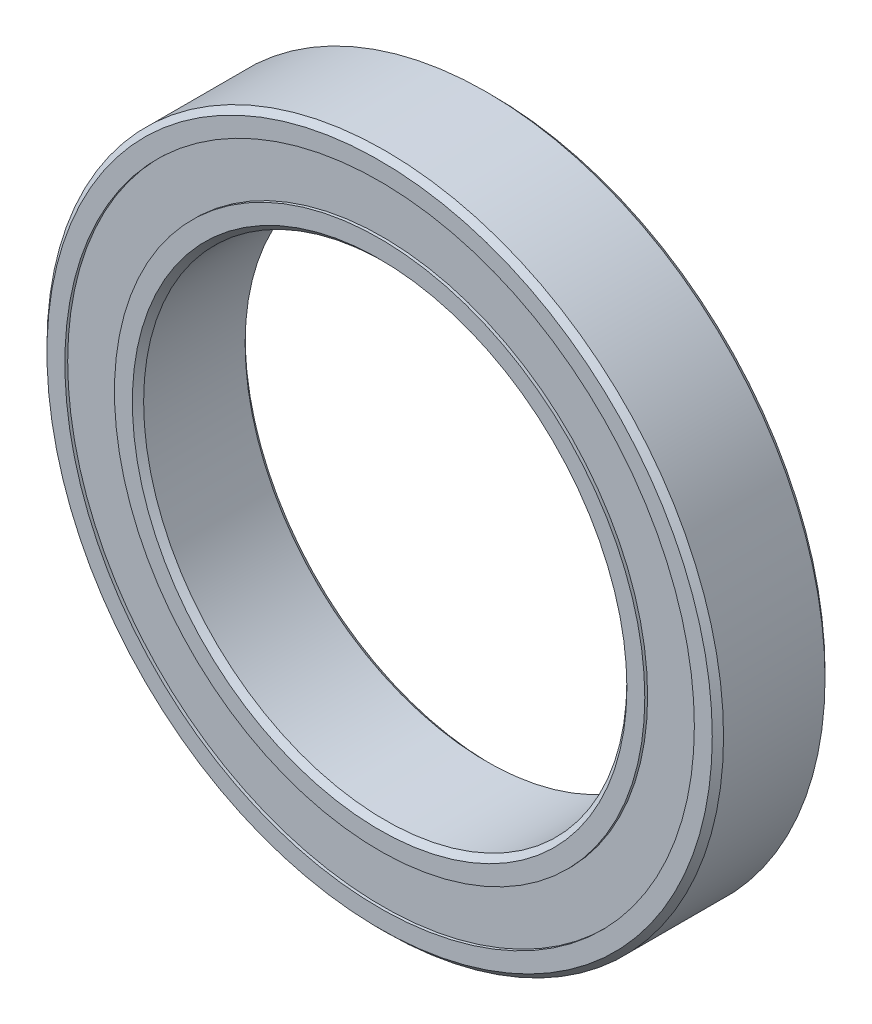
SolidWorks part; units mm, degrees
ref_plane "Front Plane" through (0, 0, 0) normal (0, 0, 1) x (1, 0, 0)
ref_plane "Top Plane" through (0, 0, 0) normal (0, 1, 0) x (1, 0, 0)
ref_plane "Right Plane" through (0, 0, 0) normal (1, 0, 0) x (0, 0, -1)
sketch "Sketch1" plane through (0, 0, 0) normal (0, 0, 1) x (1, 0, 0)
  circle A0 centre (0, 0) radius 21 construction
  circle A1 centre (0, 0) radius 14.9995 construction
  dimension "OD" = 42
  dimension "Shaft Dia" = 29.999
sketch "Sketch2" plane through (0, 0, 0) normal (1, 0, 0) x (0, 0, -1)
  line L0 (-3.5, 0) -> (3.5, 0) construction
  line L1 (0, 21) -> (0, -21) construction
  line L2 (3.15, 21) -> (-3.15, 21) construction
  line L3 (-3.15, 21) -> (-3.5, 20.65) construction
  line L4 (-3.5, 20.65) -> (-3.5, 19.5382) construction
  line L5 (-3.5, 19.5382) -> (-1.5556, 19.5382) construction
  line L6 (3.5, 19.5382) -> (1.5556, 19.5382) construction
  line L7 (3.5, 20.65) -> (3.5, 19.5382) construction
  line L8 (3.15, 21) -> (3.5, 20.65) construction
  line L9 (0, 21) -> (0, 17.9998) construction
  line L10 (0, 17.9998) -> (0, 14.9995) construction
  line L11 (3.5, 17.9998) -> (-3.5, 17.9998) construction
  line L12 (-3.5, 15.3495) -> (-3.5, 16.4613) construction
  line L13 (-3.15, 14.9995) -> (-3.5, 15.3495) construction
  line L14 (3.15, 14.9995) -> (-3.15, 14.9995) construction
  line L15 (3.15, 14.9995) -> (3.5, 15.3495) construction
  line L16 (3.5, 15.3495) -> (3.5, 16.4613) construction
  line L17 (3.5, 16.4613) -> (1.5556, 16.4613) construction
  line L18 (-3.5, 16.4613) -> (-1.5556, 16.4613) construction
  arc A0 (-1.5556, 19.5382) -> (1.5556, 19.5382) centre (0, 17.9998) cw construction
  arc A1 (-1.5556, 16.4613) -> (1.5556, 16.4613) centre (0, 17.9998) ccw construction
  point P14 (0, 14.9995)
  point P18 (0, 17.9998)
  dimension "D1" = 45
  dimension "D2" = 0.35
  dimension "D3" = 3.1111
  dimension "D4" = 1.5385
  dimension "Width" = 7
sketch "Sketch6" plane through (0, 0, 0) normal (1, 0, 0) x (0, 0, -1)
  line L0 (-3.5, 20.65) -> (-3.5, 19.5382) construction
  line L1 (-3.15, 21) -> (-3.5, 20.65) construction
  line L2 (3.15, 21) -> (-3.15, 21) construction
  line L3 (3.15, 21) -> (3.5, 20.65) construction
  line L4 (3.5, 20.65) -> (3.5, 19.5382) construction
  line L5 (3.5, 19.5382) -> (1.5556, 19.5382) construction
  line L6 (-3.5, 19.5382) -> (-1.5556, 19.5382) construction
  line L7 (-3.5, 20.65) -> (-3.5, 19.5382)
  line L8 (-3.15, 21) -> (-3.5, 20.65)
  line L9 (3.15, 21) -> (-3.15, 21)
  line L10 (3.15, 21) -> (3.5, 20.65)
  line L11 (3.5, 20.65) -> (3.5, 19.5382)
  line L12 (3.5, 19.5382) -> (1.5556, 19.5382)
  line L13 (-3.5, 19.5382) -> (-1.5556, 19.5382)
  line L14 (-3.5, 15.3495) -> (-3.5, 16.4613) construction
  line L15 (-3.15, 14.9995) -> (-3.5, 15.3495) construction
  line L16 (3.15, 14.9995) -> (-3.15, 14.9995) construction
  line L17 (3.15, 14.9995) -> (3.5, 15.3495) construction
  line L18 (3.5, 15.3495) -> (3.5, 16.4613) construction
  line L19 (3.5, 16.4613) -> (1.5556, 16.4613) construction
  line L20 (-3.5, 16.4613) -> (-1.5556, 16.4613) construction
  line L21 (-3.5, 15.3495) -> (-3.5, 16.4613)
  line L22 (-3.15, 14.9995) -> (-3.5, 15.3495)
  line L23 (3.15, 14.9995) -> (-3.15, 14.9995)
  line L24 (3.15, 14.9995) -> (3.5, 15.3495)
  line L25 (3.5, 15.3495) -> (3.5, 16.4613)
  line L26 (3.5, 16.4613) -> (1.5556, 16.4613)
  line L27 (-3.5, 16.4613) -> (-1.5556, 16.4613)
  arc A0 (1.5556, 19.5382) -> (-1.5556, 19.5382) centre (0, 17.9998) ccw construction
  arc A1 (1.5556, 19.5382) -> (-1.5556, 19.5382) centre (0, 17.9998) ccw
  arc A2 (-1.5556, 16.4613) -> (1.5556, 16.4613) centre (0, 17.9998) ccw construction
  arc A3 (-1.5556, 16.4613) -> (1.5556, 16.4613) centre (0, 17.9998) ccw
revolve "Revolve1" add sketch "Sketch6" angle 360 about L0
sketch "Sketch4" plane through (0, 0, 0) normal (1, 0, 0) x (0, 0, -1)
  line L0 (-2.1878, 17.9998) -> (2.1878, 17.9998)
  arc A2 (-2.1878, 17.9998) -> (2.1878, 17.9998) centre (0, 17.9998) cw
  arc A3 (1.5556, 19.5382) -> (-1.5556, 19.5382) centre (0, 17.9998) ccw construction
revolve "Revolve2" add sketch "Sketch4" angle 360 about L0
ref_axis "Axis1" through (0, 0, -3.5) along (0, 0, 1)
pattern_circular "CirPattern1" count 12 every 30 about axis through (0, 0, -3.5) along (0, 0, 1) of bodies 104
sketch "Sketch5" plane through (0, 0, 0) normal (1, 0, 0) x (0, 0, -1)
  line L0 (-3.5, 19.5382) -> (-1.5556, 19.5382) construction
  line L1 (-3.325, 19.5382) -> (-2.1878, 19.5382)
  line L2 (-3.325, 19.5382) -> (-3.325, 16.4613)
  line L3 (-3.325, 16.4613) -> (-2.1878, 16.4613)
  line L4 (-2.1878, 19.5382) -> (-2.1878, 16.4613)
  line L6 (3.5, 19.5382) -> (1.5556, 19.5382) construction
  line L7 (3.325, 19.5382) -> (2.1878, 19.5382)
  line L8 (3.325, 19.5382) -> (3.325, 16.4613)
  line L9 (3.325, 16.4613) -> (2.1878, 16.4613)
  line L10 (2.1878, 19.5382) -> (2.1878, 16.4613)
  line L12 (-3.15, 21) -> (-3.5, 20.65) construction
  line L13 (-3.5, 16.4613) -> (-1.5556, 16.4613) construction
  line L14 (3.5, 16.4613) -> (1.5556, 16.4613) construction
  point P18 (-3.325, 20.825)
revolve "Revolve3" add sketch "Sketch5" angle 360 about L0
equation "\"D2@Sketch2\"= \"Width@Sketch2\" * .05"
equation "\"D3@Sketch2\"=\"Width@Sketch2\" / 2.25"
equation "\"D4@Sketch2\"= ( ( ( \"OD@Sketch1\" - \"Width@Sketch2\" ) / 2 ) / 3.25 ) / 3.5"
equation "\"D2@CirPattern1\" = 360/\"Balls@CirPattern1\""
